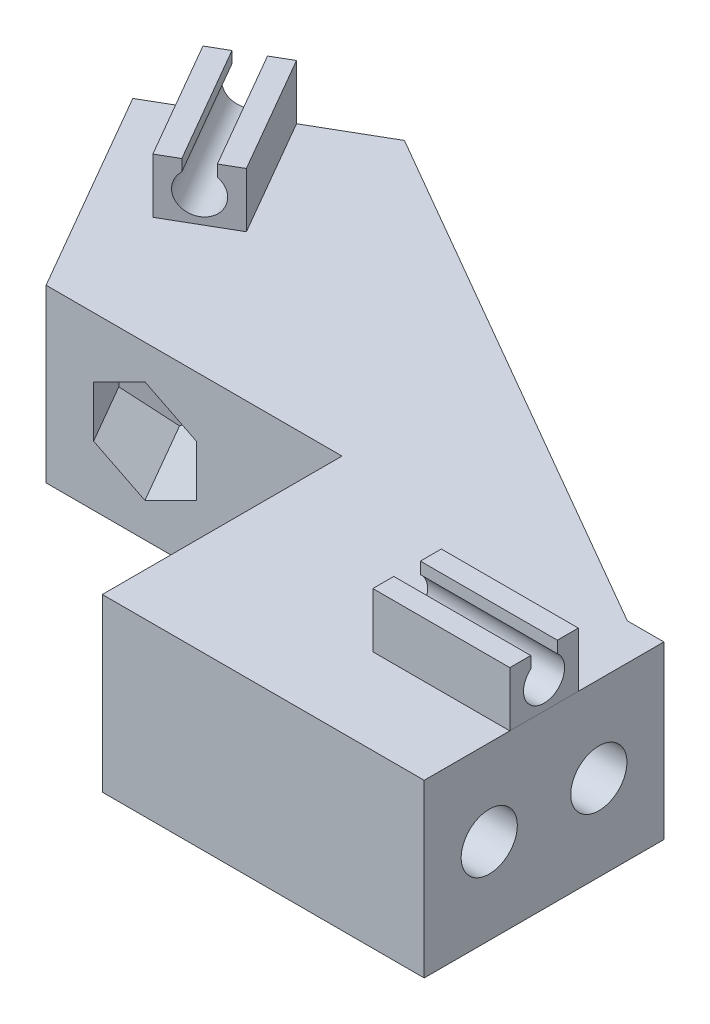
SolidWorks part; units mm, degrees
ref_plane "Спереди" through (0, 0, 0) normal (0, 0, 1) x (1, 0, 0)
ref_plane "Сверху" through (0, 0, 0) normal (0, 1, 0) x (1, 0, 0)
ref_plane "Справа" through (0, 0, 0) normal (1, 0, 0) x (0, 0, -1)
sketch "Sketch1" plane through (0, 0, 0) normal (0, 1, 0) x (1, 0, 0)
  line L0 (-40.4441, 58.3949) -> (-2.9441, -6.5571)
  line L1 (-2.9441, -6.5571) -> (67.0559, -6.5571)
  line L2 (67.0559, -6.5571) -> (67.0559, 28.4429)
  line L3 (67.0559, 28.4429) -> (5.7162, 28.4429)
  line L4 (5.7162, 28.4429) -> (-18.7935, 70.8949)
  line L5 (-18.7935, 70.8949) -> (-40.4441, 58.3949)
  dimension "D1" = 120
  dimension "D2" = 25
  dimension "D3" = 70
  dimension "D4" = 75
  dimension "D5" = 35
extrude "Boss-Extrude1" add sketch "Sketch1" along normal blind 25
sketch "Sketch2" plane through (67.0559, 0, 0) normal (1, 0, 0) x (0, 0, -1)
  line L0 (28.4429, 12.5) -> (-6.5571, 12.5) construction
  line L1 (28.4429, 25) -> (28.4429, 0) construction
  line L2 (-6.5571, 25) -> (-6.5571, 0) construction
  circle A0 centre (2.9429, 12.5) radius 4.1
  circle A1 centre (18.9429, 12.5) radius 4.1
  circle A2 centre (2.9429, 12.5) radius 8 construction
  circle A3 centre (18.9429, 12.5) radius 8 construction
  point P12 (10.9429, 12.5)
  dimension "D1" = 8.2
  dimension "D3" = 16
  dimension "D2" = 16
  dimension "D4" = 8
extrude "Cut-Extrude1" cut sketch "Sketch2" against normal through all
sketch "Sketch3" plane through (-35.3967, 0, -61.3089) normal (-0.5, 0, -0.866) x (-0.866, 0, 0.5)
  line L0 (-6.6718, 0) -> (-6.6718, 25) construction
  line L1 (-19.1718, 0) -> (5.8282, 0) construction
  line L2 (-19.1718, 25) -> (5.8282, 25) construction
  circle A0 centre (-6.6718, 12.5) radius 4.1
  dimension "D1" = 8.2
extrude "Cut-Extrude2" cut sketch "Sketch3" against normal through all
sketch "Sketch5" plane through (-35.3967, 0, -61.3089) normal (-0.5, 0, -0.866) x (-0.866, 0, 0.5)
  line L1 (-13.167, 16.25) -> (-13.167, 8.75)
  line L2 (-13.167, 8.75) -> (-6.6718, 5)
  line L3 (-6.6718, 5) -> (-0.1766, 8.75)
  line L4 (-0.1766, 8.75) -> (-0.1766, 16.25)
  line L5 (-0.1766, 16.25) -> (-6.6718, 20)
  line L6 (-6.6718, 20) -> (-13.167, 16.25)
  line L7 (-19.1718, 25) -> (-19.1718, 0) construction
  circle A0 centre (-6.6718, 12.5) radius 7.5 construction
  dimension "D1" = 15
extrude "Cut-Extrude4" cut sketch "Sketch5" against normal through all from offset 28 offset against normal yes
chamfer "Chamfer1" distance 56 angle 30 1 edges at (5.7162, 12.5, -28.4429) first distance on face at (36.386, 12.5, -28.4429)
sketch "Sketch6" plane through (0, 0, 0) normal (0, -1, 0) x (1, 0, 0)
  line L0 (20.0559, 6.5571) -> (20.0559, -28.4429)
  line L1 (-2.9441, 6.5571) -> (67.0559, 6.5571) construction
  line L2 (20.0559, -28.4429) -> (-23.1514, -28.4429)
  line L3 (-40.4441, -58.3949) -> (-2.9441, 6.5571) construction
  line L4 (20.0559, 6.5571) -> (-2.9441, 6.5571)
  line L5 (-2.9441, 6.5571) -> (-23.1514, -28.4429)
  line L6 (67.0559, 6.5571) -> (67.0559, -28.4429) construction
  dimension "D1" = 23
extrude "Cut-Extrude5" cut sketch "Sketch6" against normal through all
sketch "Sketch7" plane through (-35.3967, 0, -61.3089) normal (-0.5, 0, -0.866) x (-0.866, 0, 0.5)
  line L0 (-6.6718, 16.6) -> (-6.6718, 39.225) construction
  line L2 (-23.2022, 25) -> (5.8282, 25) construction
  line L3 (-1.6718, 33) -> (-11.6718, 33) construction
  line L4 (-1.6718, 33) -> (-1.6718, 25)
  line L5 (-1.6718, 25) -> (-11.6718, 25)
  line L6 (-11.6718, 33) -> (-11.6718, 25)
  line L7 (-1.6718, 33) -> (-11.6718, 25) construction
  line L8 (-1.6718, 25) -> (-11.6718, 33) construction
  line L9 (-11.6718, 33) -> (-8.5718, 33)
  line L10 (-8.5718, 33) -> (-8.5718, 31.3216)
  line L11 (-8.5718, 31.3216) -> (-4.7718, 31.3216) construction
  line L13 (-4.7718, 31.3216) -> (-4.7718, 33)
  line L14 (-4.7718, 33) -> (-1.6718, 33)
  circle A1 centre (-6.6718, 12.5) radius 4.1 construction
  circle A2 centre (-6.6718, 29) radius 3 construction
  arc A3 (-8.5718, 31.3216) -> (-4.7718, 31.3216) centre (-6.6718, 29) ccw
  point P4 (-6.6718, 29)
  dimension "D3" = 6
  dimension "D1" = 8
  dimension "D2" = 10
  dimension "D4" = 3.8
extrude "Boss-Extrude2" add sketch "Sketch7" against normal blind 20
sketch "Sketch8" plane through (67.0559, 0, 0) normal (1, 0, 0) x (0, 0, -1)
  line L0 (10.9429, 25) -> (10.9429, 46.5452) construction
  line L2 (-6.5571, 25) -> (28.4429, 25) construction
  line L3 (5.9429, 33) -> (9.0026, 33)
  line L4 (5.9429, 33) -> (15.9429, 33) construction
  line L5 (5.9429, 33) -> (5.9429, 25)
  line L6 (5.9429, 25) -> (15.9429, 25)
  line L7 (15.9429, 33) -> (15.9429, 25)
  line L8 (5.9429, 33) -> (15.9429, 25) construction
  line L9 (5.9429, 25) -> (15.9429, 33) construction
  line L10 (9.0026, 33) -> (9.0026, 31.288)
  line L11 (9.0026, 31.288) -> (12.8833, 31.288) construction
  line L12 (12.8833, 31.288) -> (12.8833, 33)
  line L13 (12.8833, 33) -> (15.9429, 33)
  circle A0 centre (10.9429, 29) radius 3 construction
  arc A1 (9.0026, 31.288) -> (12.8833, 31.288) centre (10.9429, 29) ccw
  point P4 (10.9429, 29)
  dimension "D3" = 10
  dimension "D1" = 6
  dimension "D2" = 8
extrude "Boss-Extrude3" add sketch "Sketch8" against normal blind 20 separate body
